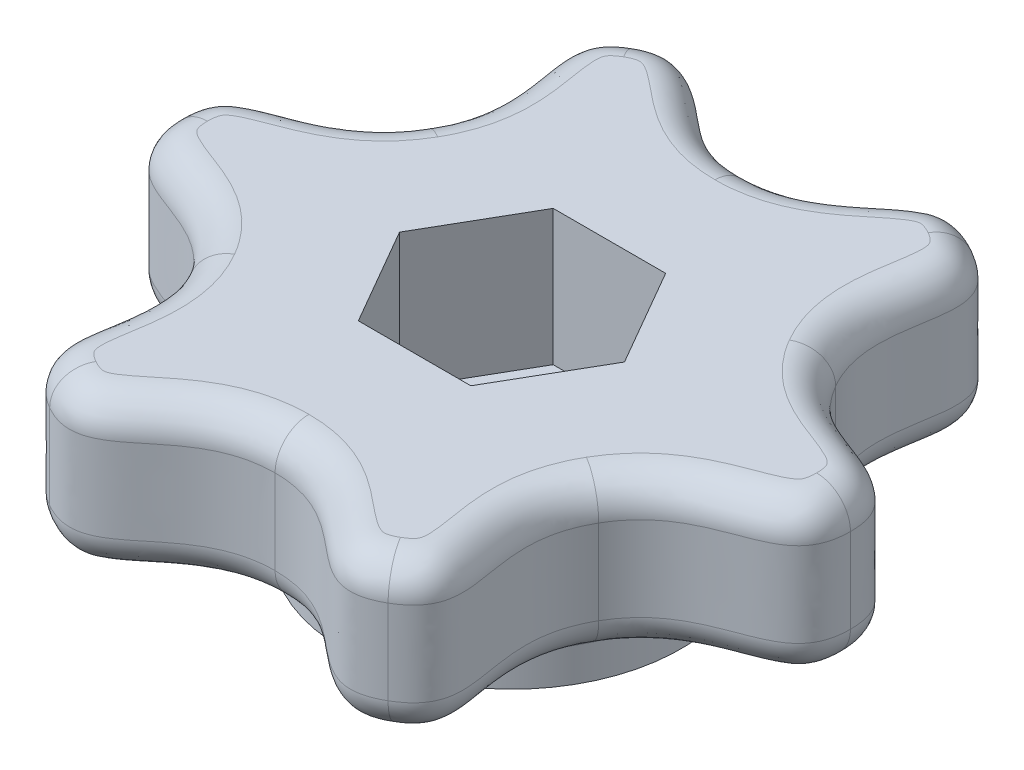
SolidWorks part; units mm, degrees
ref_plane "Front Plane" through (0, 0, 0) normal (0, 0, 1) x (1, 0, 0)
ref_plane "Top Plane" through (0, 0, 0) normal (0, 1, 0) x (1, 0, 0)
ref_plane "Right Plane" through (0, 0, 0) normal (1, 0, 0) x (0, 0, -1)
sketch "Sketch1" plane through (0, -4.3656, 0) normal (0, -1, 0) x (1, 0, 0)
  circle A1 centre (0, 0) radius 10
  circle A2 centre (0, 0) radius 3.375
  circle A3 centre (0, 0) radius 3.375
  dimension "D2" = 20
  dimension "D1" = 0.2
extrude "Boss-Extrude1" add sketch "Sketch1" along normal blind 5
sketch "Sketch2" plane through (0, -4.3656, 0) normal (0, 1, 0) x (1, 0, 0)
  line L0 (0, 0) -> (50000, 0) construction
  line L1 (0, 0) -> (43301.2702, 25000) construction
  line L2 (14.2269, 3.3582) -> (10.0218, 10.6418) construction
  line L3 (20, -2.1701) -> (20, 2.1701) construction
  line L6 (3.3234, -5.7563) -> (6.6467, 0)
  line L7 (6.6467, 0) -> (3.3234, 5.7563)
  line L8 (3.3234, 5.7563) -> (-3.3234, 5.7563)
  line L9 (-3.3234, 5.7563) -> (-6.6467, 0)
  line L10 (-6.6467, 0) -> (-3.3234, -5.7563)
  line L11 (-3.3234, -5.7563) -> (3.3234, -5.7563)
  line L12 (3.3234, -5.7563) -> (6.6467, 0)
  line L13 (6.6467, 0) -> (3.3234, 5.7563)
  line L14 (3.3234, 5.7563) -> (-3.3234, 5.7563)
  line L15 (-3.3234, 5.7563) -> (-6.6467, 0)
  line L16 (-6.6467, 0) -> (-3.3234, -5.7563)
  line L17 (-3.3234, -5.7563) -> (3.3234, -5.7563)
  spline S0 degree 3 poles (12.1244, 7) (14.7526, 2.4478) (20, 4.4146) (20, 0) knots 0 0 0 0 1 1 1 1
  spline S1 degree 3 poles (12.1244, -7) (14.7526, -2.4478) (20, -4.4146) (20, 0) knots 0 0 0 0 1 1 1 1
  spline S2 degree 3 poles (12.1244, -7) (9.4961, -11.5522) (13.8232, -15.1132) (10, -17.3205) knots 0 0 0 0 1 1 1 1
  spline S3 degree 3 poles (0, -14) (5.2565, -14) (6.1768, -19.5278) (10, -17.3205) knots 0 0 0 0 1 1 1 1
  spline S4 degree 3 poles (0, -14) (-5.2565, -14) (-6.1768, -19.5278) (-10, -17.3205) knots 0 0 0 0 1 1 1 1
  spline S5 degree 3 poles (-12.1244, -7) (-9.4961, -11.5522) (-13.8232, -15.1132) (-10, -17.3205) knots 0 0 0 0 1 1 1 1
  spline S6 degree 3 poles (-12.1244, -7) (-14.7526, -2.4478) (-20, -4.4146) (-20, 0) knots 0 0 0 0 1 1 1 1
  spline S7 degree 3 poles (-12.1244, 7) (-14.7526, 2.4478) (-20, 4.4146) (-20, 0) knots 0 0 0 0 1 1 1 1
  spline S8 degree 3 poles (-12.1244, 7) (-9.4961, 11.5522) (-13.8232, 15.1132) (-10, 17.3205) knots 0 0 0 0 1 1 1 1
  spline S9 degree 3 poles (0, 14) (-5.2565, 14) (-6.1768, 19.5278) (-10, 17.3205) knots 0 0 0 0 1 1 1 1
  spline S10 degree 3 poles (0, 14) (5.2565, 14) (6.1768, 19.5278) (10, 17.3205) knots 0 0 0 0 1 1 1 1
  spline S11 degree 3 poles (12.1244, 7) (9.4961, 11.5522) (13.8232, 15.1132) (10, 17.3205) knots 0 0 0 0 1 1 1 1
  point P36 (0, 0)
  point P37 (0, 0)
  dimension "D2" = 20
  dimension "D3" = 14
  dimension "D1" = 0.2
extrude "Boss-Extrude2" add sketch "Sketch2" along normal blind 8 and the other way blind 1
fillet "Fillet1" radius 2 24 edges
fillet "Fillet2" radius 2 1 edges at (0, -5.3656, 10)
